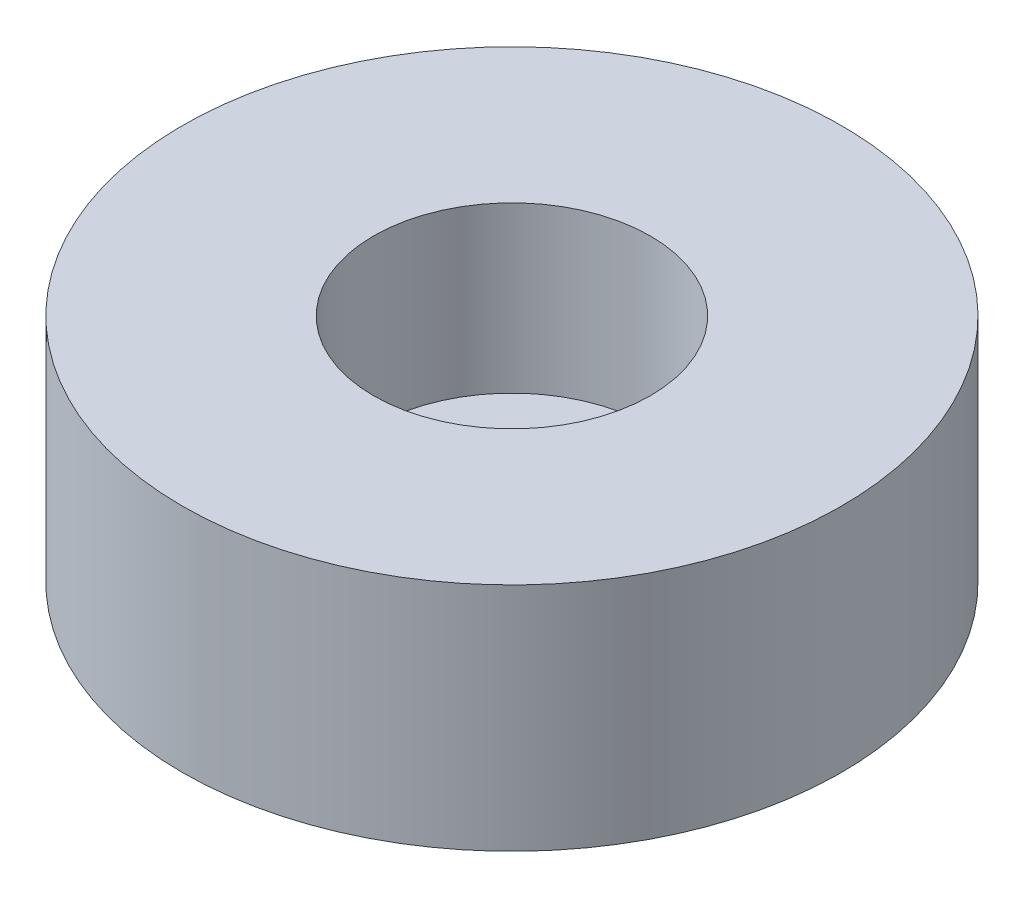
SolidWorks part; units mm, degrees
ref_plane "Front Plane" through (0, 0, 0) normal (0, 0, 1) x (1, 0, 0)
ref_plane "Top Plane" through (0, 0, 0) normal (0, 1, 0) x (1, 0, 0)
ref_plane "Right Plane" through (0, 0, 0) normal (1, 0, 0) x (0, 0, -1)
sketch "Sketch1" plane through (0, 0, 0) normal (0, 1, 0) x (1, 0, 0)
  circle A0 centre (0, 0) radius 4.2
  circle A1 centre (0, 0) radius 10
  dimension "D1" = 8.4
  dimension "D2" = 20
extrude "Boss-Extrude1" add sketch "Sketch1" along normal blind 5
extrude "Boss-Extrude2" add sketch "Sketch1<2>" against normal blind 2 contours A1 A0 | A0 region at (0, 0, 0) region at (-9.7172, 0, 0)
sketch "Sketch1<2>" plane through (0, 0, 0) normal (0, 1, 0) x (1, 0, 0) same geometry as "Sketch1"
